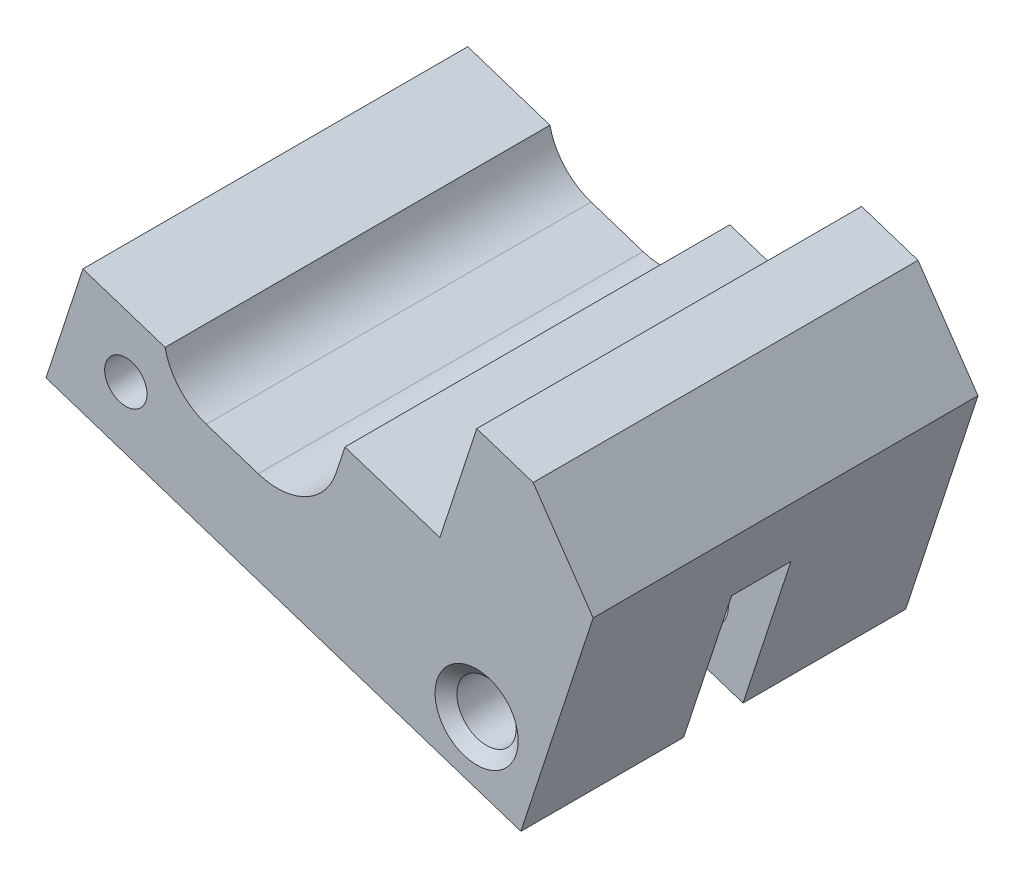
SolidWorks part; units mm, degrees
material "6061-T6 (SS)"
ref_plane "Front Plane" through (0, 0, 0) normal (0, 0, 1) x (1, 0, 0)
ref_plane "Top Plane" through (0, 0, 0) normal (0, 1, 0) x (1, 0, 0)
ref_plane "Right Plane" through (0, 0, 0) normal (1, 0, 0) x (0, 0, -1)
sketch "Sketch1" plane through (0, 0, 0) normal (0, 0, 1) x (1, 0, 0)
  line L0 (7.0876, -81.9967) -> (12.0212, -66.9078) construction
  line L1 (8.0167, -68.9388) -> (7.03, -71.9566)
  line L2 (0.0077, -73.001) -> (-12.0634, -69.0541)
  line L3 (-14.0369, -75.0896) -> (11.3653, -83.3954)
  line L4 (12.0212, -66.9078) -> (15.2291, -71.5783)
  line L6 (8.0167, -68.9388) -> (11.0345, -69.9256) construction
  line L7 (9.0034, -65.9211) -> (8.0167, -68.9388)
  line L8 (12.0212, -66.9078) -> (9.0034, -65.9211)
  line L9 (-12.0634, -69.0541) -> (-14.0369, -75.0896)
  line L10 (11.3653, -83.3954) -> (15.2291, -71.5783)
  line L11 (-42.3168, -73.5908) -> (-38.467, -73.5908) construction
  line L13 (7.03, -71.9566) -> (0.9944, -69.9832)
  line L14 (0.9944, -69.9832) -> (0.0077, -73.001)
  dimension "D2" = 19.05
  dimension "D3" = 15.875
  dimension "D4" = 3.175
  dimension "D5" = 3.175
  dimension "D6" = 6.35
  dimension "D7" = 3.175
  dimension "D8" = 6.35
extrude "Boss-Extrude1" add sketch "Sketch1" along normal offset from surface (20.5861 mm away) 1.27 from offset 1.27
hole_wizard "#4-40 Tapped Hole1" positions "Sketch3" profile "Sketch2" tap size "#4-40" standard "ANSI Inch" end condition through all
sketch "Sketch3" plane through (0, 0, 21.8561) normal (0, 0, 1) x (1, 0, 0)
  line L0 (-14.0369, -75.0896) -> (-12.0634, -69.0541) construction
  line L1 (-13.0501, -72.0719) -> (12.352, -80.3776) construction
  line L2 (15.2291, -71.5783) -> (11.3653, -83.3954) construction
  line L4 (11.3653, -83.3954) -> (-14.0369, -75.0896) construction
  point P0 (-9.7668, -73.1454)
  dimension "D1" = 3.4544
sketch "Sketch2" plane through (-9.7668, -73.1454, 21.8561) normal (1, 0, 0) x (0, -1, 0)
  line L0 (0, 0) -> (0, 20.5861)
  line L1 (0, 20.5861) -> (1.1303, 20.5861)
  line L2 (1.1303, 20.5861) -> (1.1303, 0)
  line L5 (1.1303, 0) -> (0, 0)
  line L11 (0, -6.35) -> (0, 107.95) construction
  dimension "Thru Tap Drill Dia." = 2.2606
  dimension "Thru Tap Drill Depth" = 20.5861
cosmetic thread "Hole Thread1" parameters "D2"=2.8448
hole_wizard "1/8 (0.125) Diameter Hole1" positions "Sketch5" profile "Sketch4" hole size "1/8" standard "ANSI Inch" end condition through all
sketch "Sketch5" plane through (0, 0, 21.8561) normal (0, 0, 1) x (1, 0, 0)
  line L0 (-13.0501, -72.0719) -> (12.352, -80.3776) construction
  line L1 (-14.0369, -75.0896) -> (-12.0634, -69.0541) construction
  line L2 (15.2291, -71.5783) -> (11.3653, -83.3954) construction
  line L6 (11.3653, -83.3954) -> (-14.0369, -75.0896) construction
  line L7 (8.9976, -79.2808) -> (2.5847, -98.894) construction
  line L9 (-2.6048, -102.1841) -> (-15.6885, -142.1994) construction
  point P15 (8.9976, -79.2808)
sketch "Sketch4" plane through (8.9976, -79.2808, 21.8561) normal (1, 0, 0) x (0, -1, 0)
  line L0 (0, 0) -> (0, 20.5861)
  line L1 (0, 20.5861) -> (1.5875, 20.5861)
  line L2 (1.5875, 20.5861) -> (1.5875, 0.5328)
  line L3 (1.5875, 0.5328) -> (2.2225, 0)
  line L5 (2.2225, 0) -> (0, 0)
  line L6 (-1.5875, 0.5328) -> (-2.2225, 0) construction
  line L11 (0, -6.35) -> (0, 107.95) construction
  dimension "Thru Hole Dia." = 3.175
  dimension "Thru Hole Depth" = 20.5861
  dimension "Near C'Sink Dia." = 4.445
  dimension "Near C'Sink Angle" = 100
sketch "Sketch6" plane through (-23.5364, -71.9836, 0) normal (-0.3108, -0.9505, 0) x (0.9505, -0.3108, 0)
  line L0 (36.72, 11.5631) -> (26.56, 11.5631) construction
  line L1 (36.72, 21.8561) -> (36.72, 1.27) construction
  line L2 (36.72, 21.8561) -> (9.9944, 21.8561) construction
  line L3 (36.72, 13.1506) -> (26.56, 13.1506)
  line L4 (36.72, 9.9756) -> (26.56, 9.9756)
  arc A0 (36.72, 13.1506) -> (36.72, 9.9756) centre (36.72, 11.5631) cw
  arc A1 (26.56, 13.1506) -> (26.56, 9.9756) centre (26.56, 11.5631) ccw
  dimension "D1" = 10.16
  dimension "D2" = 1.5875
  dimension "D3" = 1.5875
extrude "Cut-Extrude1" cut sketch "Sketch6" against normal blind 8.255
sketch "Sketch8" plane through (0, 0, 21.8561) normal (0, 0, 1) x (1, 0, 0)
  line L0 (-1.6596, -70.7188) -> (-4.4359, -69.811) construction
  line L1 (-2.6857, -73.8573) -> (-5.4621, -72.9495)
  line L2 (-0.6334, -67.5803) -> (-3.4097, -66.6725)
  line L5 (11.3653, -83.3954) -> (-14.0369, -75.0896) construction
  line L7 (2.765, -71.8983) -> (0.1995, -79.7445) construction
  line L8 (-12.0634, -69.0541) -> (0.0077, -73.001) construction
  line L9 (1.4789, -71.745) -> (1.9526, -70.2965)
  line L10 (0.9944, -69.9832) -> (7.03, -71.9566) construction
  line L11 (1.9526, -70.2965) -> (1.5983, -70.1806)
  arc A0 (-2.6857, -73.8573) -> (-0.6334, -67.5803) centre (-1.6596, -70.7188) ccw
  arc A1 (-3.4097, -66.6725) -> (-5.4621, -72.9495) centre (-4.4359, -69.811) ccw
  point P2 (-3.0477, -70.2649)
  point P9 (1.4789, -71.745)
  point P12 (-7.5744, -68.7848)
  line M10 (7.03, -71.9566) -> (0.9944, -69.9832)
  line M11 (0.9944, -69.9832) -> (0.0077, -73.001)
  line M12 (0.0077, -73.001) -> (-12.0634, -69.0541)
  dimension "D1" = 3.302
  dimension "D2" = 1.27
  dimension "D3" = 1.651
  dimension "D4" = 9.525
extrude "Cut-Extrude2" cut sketch "Sketch8" against normal through all contours A1 L1 A0 M12 M10 M11 | A0 L9 M10 region at (-2.8728, -72.3569, 21.8561) region at (1.7304, -70.62, 21.8561)
